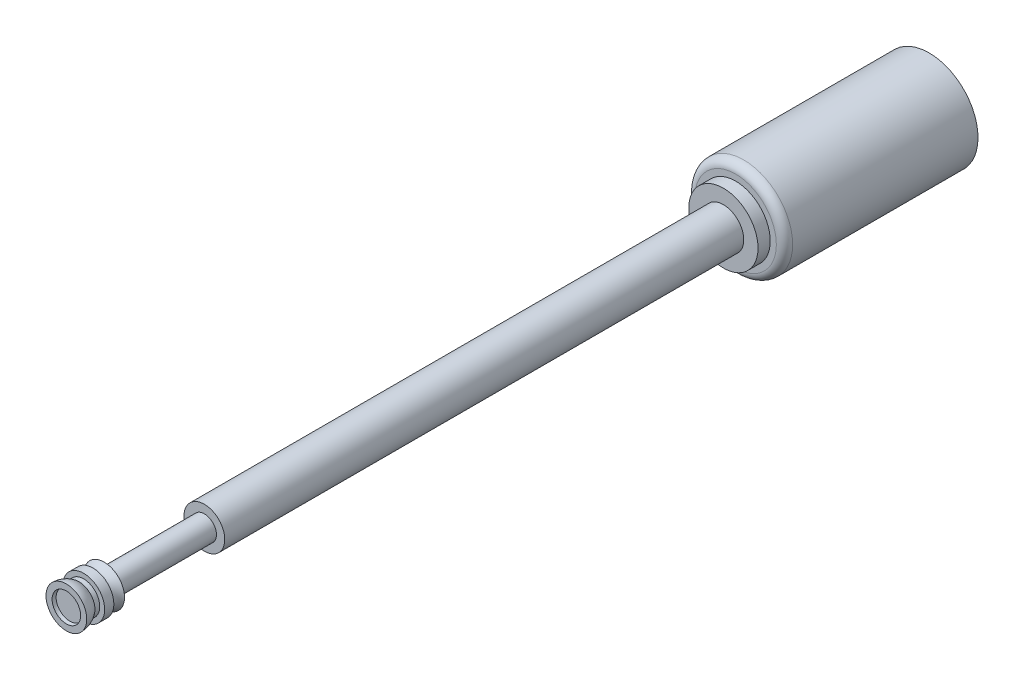
SolidWorks part; units mm, degrees
ref_plane "Front Plane" through (0, 0, 0) normal (0, 0, 1) x (1, 0, 0)
ref_plane "Top Plane" through (0, 0, 0) normal (0, 1, 0) x (1, 0, 0)
ref_plane "Right Plane" through (0, 0, 0) normal (1, 0, 0) x (0, 0, -1)
sketch "Sketch1" plane through (0, 0, 0) normal (0, 0, 1) x (1, 0, 0)
  circle A0 centre (0, 0) radius 0.5
  circle A1 centre (0, 0) radius 1.2
  dimension "D1" = 1
  dimension "D2" = 2.4
extrude "Boss-Extrude1" add sketch "Sketch1" along normal blind 15.5 contours A0 region at (0, 0, 0)
extrude "Boss-Extrude2" add sketch "Sketch1<3>" against normal blind 4.75 separate body contours A1 A0 region at (-1.1661, 0, 0)
sketch "Sketch1<3>" plane through (0, 0, 0) normal (0, 0, 1) x (1, 0, 0) same geometry as "Sketch1"
fillet "Fillet1" radius 0.2 1 edges at (1.2, 0, 0)
sketch "Sketch2" plane through (0, 0, 0) normal (0, 0, 1) x (1, 0, 0)
  circle A0 centre (0, 0) radius 0.85
  dimension "D1" = 1.7
extrude "Boss-Extrude3" add sketch "Sketch2" along normal blind 0.3
sketch "Sketch3" plane through (0, 0, 0) normal (0, 1, 0) x (1, 0, 0)
  line L0 (0.5, -15.5) -> (0, -15.5)
  line L1 (-0.5, -15.5) -> (0.5, -15.5) construction
  line L2 (0, -15.5) -> (0, -16.0775)
  line L3 (0.35, -16.4275) -> (0.5, -16.4275)
  line L4 (0.3946, -16.1204) -> (0.3946, -16.002)
  line L5 (0.3946, -16.002) -> (0.5133, -16.002)
  line L6 (0.5133, -16.002) -> (0.5133, -15.7759)
  line L7 (0.5133, -15.7759) -> (0.3869, -15.7759)
  arc A0 (0, -16.0775) -> (0.35, -16.4275) centre (0, -16.4275) cw
  arc A1 (0.5, -16.4275) -> (0.3946, -16.1204) centre (0, -16.4275) ccw
  arc A2 (0.3869, -15.7759) -> (0.5, -15.5) centre (0.7799, -15.7759) cw
  point P9 (0.5661, -17.677)
  point P17 (0.3929, -15.7392)
  point P18 (0, -16.8603)
  point P19 (0.226, -15.9675)
  point P20 (0, -16.1859)
  point P21 (0.2221, -15.8717)
  point P22 (0, -15.9407)
  point P23 (0.425, -16.4275)
  point P24 (0.3538, -15.7376)
  point P25 (0, 0)
  point P26 (0.3792, -15.7337)
  point P27 (0.3907, -15.9445)
  point P28 (0.3856, -16.1093)
  point P29 (0.3501, -16.0775)
  point P30 (0, 0)
  point P31 (0.3858, -16.1095)
  point P32 (0.3516, -16.0775)
  point P33 (0.3869, -15.7759)
  point P34 (0.3716, -16.002)
  point P35 (0.3946, -16.002)
  dimension "D2" = 0.35
  dimension "D3" = 0.5
  dimension "D1" = 0.9275
revolve "Revolve1" add sketch "Sketch3" angle 360 about L2
sketch "Sketch4" plane through (0, 0, 0) normal (0, 1, 0) x (1, 0, 0)
  line L0 (0, -15.5) -> (0, -16.4275) construction
  line L1 (0.5, -15.5) -> (-0.5, -15.5) construction
  line L2 (-0.5, -16.4275) -> (0.5, -16.4275) construction
  line L4 (0, -16.3055) -> (-0.4656, -16.3055)
  line L5 (0, -16.3055) -> (0, -16.34)
  line L6 (0, -16.34) -> (-0.4656, -16.34)
  line L7 (-0.4656, -16.3055) -> (-0.4656, -16.34)
  dimension "D1" = 0.84
revolve "Revolve2" add sketch "Sketch4" angle 360 about L5
sketch "Sketch5" plane through (0, 0, 0) normal (0, 1, 0) x (1, 0, 0)
  line L0 (0.5, -15.5) -> (-0.5, -15.5) construction
  line L1 (-0.2962, -15.5) -> (-1.5537, -15.5)
  line L2 (-0.2962, -15.5) -> (-0.2962, -13.04)
  line L3 (-0.2962, -13.04) -> (-1.5537, -13.04)
  line L4 (-1.5537, -15.5) -> (-1.5537, -13.04)
  line L5 (0, -15.5) -> (0, -16.4275) construction
  line L6 (-0.5, -16.4275) -> (0.5, -16.4275) construction
  dimension "D1" = 2.46
  dimension "D2" = 0.2962
revolve "Cut-Revolve1" cut sketch "Sketch5" angle 360 about L5
sketch "Sketch6" plane through (0, 0, -4.75) normal (0, 0, -1) x (-1, 0, 0)
  circle A0 centre (0, 0) radius 0.5 construction
  circle A1 centre (0, 0) radius 0.5
extrude "Boss-Extrude4" add sketch "Sketch6" against normal blind 2.84
sketch "Sketch7" plane through (0, 0, -4.75) normal (0, 0, -1) x (-1, 0, 0)
  point P0 (0, 0)
